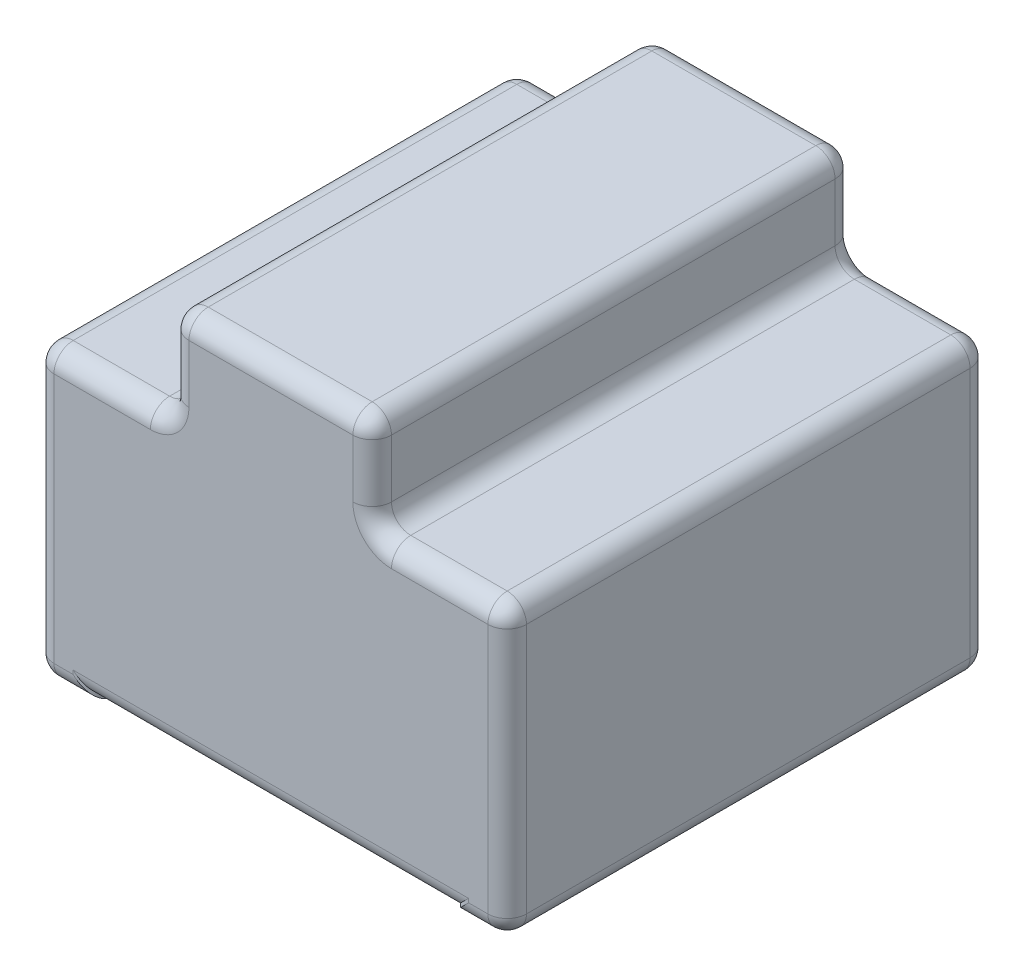
SolidWorks part; units mm, degrees
ref_plane "Front Plane" through (0, 0, 0) normal (0, 0, 1) x (1, 0, 0)
ref_plane "Top Plane" through (0, 0, 0) normal (0, 1, 0) x (1, 0, 0)
ref_plane "Right Plane" through (0, 0, 0) normal (1, 0, 0) x (0, 0, -1)
sketch "Sketch2" plane through (0, 0, 0) normal (0, 0, 1) x (1, 0, 0)
  line L0 (0, 0) -> (0, 38.1)
  line L1 (0, 38.1) -> (17.78, 38.1)
  line L2 (17.78, 38.1) -> (17.78, 50.8)
  line L3 (17.78, 50.8) -> (44.45, 50.8)
  line L4 (44.45, 50.8) -> (44.45, 38.1)
  line L5 (44.45, 38.1) -> (62.23, 38.1)
  line L6 (62.23, 38.1) -> (62.23, 0)
  line L8 (54.61, 0) -> (62.23, 0)
  line L9 (54.61, 0) -> (54.61, 0.508)
  line L10 (54.61, 0.508) -> (7.62, 0.508)
  line L11 (7.62, 0.508) -> (7.62, 0)
  line L12 (7.62, 0) -> (0, 0)
  dimension "D1" = 38.1
  dimension "D2" = 12.7
  dimension "D3" = 12.7
  dimension "D4" = 17.78
  dimension "D5" = 17.78
  dimension "D6" = 7.62
  dimension "D7" = 7.62
  dimension "D8" = 46.99
  dimension "D9" = 0.508
  dimension "D10" = 38.1
extrude "Boss-Extrude1" add sketch "Sketch2" along normal blind 58.42
sketch "Sketch3" plane through (0, 0.508, 0) normal (0, -1, 0) x (1, 0, 0)
  line L0 (7.62, 58.42) -> (54.61, 58.42) construction
  line L1 (7.62, 0) -> (54.61, 0) construction
  line L2 (7.62, 58.42) -> (7.62, 0) construction
  line L3 (54.61, 58.42) -> (54.61, 0) construction
  line L12 (10.16, 3.81) -> (52.07, 3.81)
  line L13 (52.07, 3.81) -> (52.07, 54.61)
  line L14 (52.07, 54.61) -> (10.16, 54.61)
  line L15 (10.16, 54.61) -> (10.16, 3.81)
  dimension "D1" = 3.81
  dimension "D2" = 3.81
  dimension "D3" = 2.54
  dimension "D4" = 2.54
extrude "Cut-Extrude1" cut sketch "Sketch3" against normal blind 2.54
sketch "Sketch15" plane through (0, 0.508, 0) normal (0, -1, 0) x (-1, 0, 0)
  line L0 (-52.07, -29.21) -> (-10.16, -29.21) construction
  line L1 (-52.07, -3.81) -> (-52.07, -54.61) construction
  line L2 (-10.16, -54.61) -> (-10.16, -3.81) construction
  line L3 (-52.07, -29.21) -> (-52.07, -54.61)
  line L4 (-52.07, -54.61) -> (-10.16, -54.61)
  line L6 (-10.16, -54.61) -> (-10.16, -29.21)
  line L7 (-10.16, -3.81) -> (-52.07, -3.81) construction
  line L8 (-52.07, -54.61) -> (-10.16, -54.61) construction
  line L9 (-52.07, -29.21) -> (-10.16, -29.21)
  dimension "D1" = 0
revolve "Cut-Revolve2" cut sketch "Sketch15" angle 360 about L0
sketch "Sketch17" plane through (0, 0.508, 0) normal (0, -1, 0) x (1, 0, 0)
  line L0 (52.07, 3.81) -> (52.07, 54.61) construction
  line L1 (46.99, 1.27) -> (15.24, 1.27)
  line L2 (46.99, 1.27) -> (46.99, 29.21)
  line L3 (46.99, 29.21) -> (15.24, 29.21)
  line L4 (15.24, 1.27) -> (15.24, 29.21)
  line L5 (7.62, 58.42) -> (7.62, 0) construction
  line L6 (54.61, 58.42) -> (54.61, 0) construction
  line L7 (7.62, 0) -> (54.61, 0) construction
  point P12 (52.07, 29.21)
  dimension "D1" = 0
  dimension "D2" = 7.62
  dimension "D3" = 7.62
  dimension "D4" = 1.27
revolve "Cut-Revolve3" cut sketch "Sketch17" angle 230 about L3 other way angle 20
sketch "Sketch18" plane through (0, 0.508, 0) normal (0, -1, 0) x (1, 0, 0)
  line L0 (10.16, 3.81) -> (15.24, 3.81) construction
  line L1 (52.07, 29.21) -> (46.99, 29.21)
  line L2 (52.07, 29.21) -> (52.07, 47.752)
  line L3 (52.07, 47.752) -> (46.99, 47.752)
  line L4 (46.99, 29.21) -> (46.99, 47.752)
  line L5 (10.16, 47.752) -> (15.24, 47.752)
  line L6 (10.16, 47.752) -> (10.16, 29.21)
  line L7 (10.16, 29.21) -> (15.24, 29.21)
  line L8 (15.24, 47.752) -> (15.24, 29.21)
  line L33 (52.07, 3.81) -> (52.07, 54.61) construction
  line L34 (10.16, 29.21) -> (52.07, 29.21) construction
  line L35 (10.16, 54.61) -> (52.07, 54.61) construction
  line L36 (15.24, 57.15) -> (15.24, 54.61) construction
  line L38 (46.99, 54.61) -> (46.99, 57.15) construction
  line L41 (10.16, 47.752) -> (7.62, 47.752)
  line L42 (10.16, 47.752) -> (10.16, 44.196)
  line L43 (10.16, 44.196) -> (7.62, 44.196)
  line L44 (7.62, 47.752) -> (7.62, 44.196)
  line L45 (10.16, 54.61) -> (15.24, 54.61) construction
  line L46 (52.07, 47.752) -> (54.61, 47.752)
  line L47 (52.07, 47.752) -> (52.07, 44.196)
  line L48 (52.07, 44.196) -> (54.61, 44.196)
  line L49 (54.61, 47.752) -> (54.61, 44.196)
  line L51 (10.16, 54.61) -> (10.16, 3.81) construction
  point P34 (12.7, 3.81)
  dimension "D1" = 25.4
  dimension "D2" = 6.858
  dimension "D3" = 3.556
  dimension "D4" = 6.858
  dimension "D5" = 2.54
  dimension "D6" = 0
  dimension "D7" = 3.556
  dimension "D8" = 2.54
sketch "Sketch19" plane through (0, 0, 0) normal (0, 0, -1) x (-1, 0, 0)
  line L24 (-7.62, 0) -> (0, 0)
  line L25 (0, 0) -> (0, 38.1)
  line L26 (0, 38.1) -> (-17.78, 38.1)
  line L27 (-17.78, 38.1) -> (-17.78, 50.8)
  line L28 (-17.78, 50.8) -> (-44.45, 50.8)
  line L29 (-44.45, 50.8) -> (-44.45, 38.1)
  line L30 (-44.45, 38.1) -> (-62.23, 38.1)
  line L31 (-62.23, 38.1) -> (-62.23, 0)
  line L32 (-62.23, 0) -> (-54.61, 0)
  line L33 (-54.61, 0) -> (-54.61, 0.508)
  line L34 (-54.61, 0.508) -> (-7.62, 0.508)
  line L35 (-7.62, 0.508) -> (-7.62, 0)
  line L36 (-7.62, 0) -> (0, 0)
  line L37 (0, 0) -> (0, 38.1)
  line L38 (0, 38.1) -> (-17.78, 38.1)
  line L39 (-17.78, 38.1) -> (-17.78, 50.8)
  line L40 (-17.78, 50.8) -> (-44.45, 50.8)
  line L41 (-44.45, 50.8) -> (-44.45, 38.1)
  line L42 (-44.45, 38.1) -> (-62.23, 38.1)
  line L43 (-62.23, 38.1) -> (-62.23, 0)
  line L44 (-62.23, 0) -> (-54.61, 0)
  line L45 (-54.61, 0) -> (-54.61, 0.508)
  line L46 (-54.61, 0.508) -> (-7.62, 0.508)
  line L47 (-7.62, 0.508) -> (-7.62, 0)
  dimension "D1" = 0
extrude "Boss-Extrude2" add sketch "Sketch19" along normal blind 2.54
sketch "Sketch20" plane through (0, 0, 58.42) normal (0, 0, 1) x (1, 0, 0)
  line L24 (0, 0) -> (7.62, 0)
  line L25 (7.62, 0) -> (7.62, 0.508)
  line L26 (7.62, 0.508) -> (54.61, 0.508)
  line L27 (54.61, 0.508) -> (54.61, 0)
  line L28 (54.61, 0) -> (62.23, 0)
  line L29 (62.23, 0) -> (62.23, 38.1)
  line L30 (62.23, 38.1) -> (44.45, 38.1)
  line L31 (44.45, 38.1) -> (44.45, 50.8)
  line L32 (44.45, 50.8) -> (17.78, 50.8)
  line L33 (17.78, 50.8) -> (17.78, 38.1)
  line L34 (17.78, 38.1) -> (0, 38.1)
  line L35 (0, 38.1) -> (0, 0)
  line L36 (0, 0) -> (7.62, 0)
  line L37 (7.62, 0) -> (7.62, 0.508)
  line L38 (7.62, 0.508) -> (54.61, 0.508)
  line L39 (54.61, 0.508) -> (54.61, 0)
  line L40 (54.61, 0) -> (62.23, 0)
  line L41 (62.23, 0) -> (62.23, 38.1)
  line L42 (62.23, 38.1) -> (44.45, 38.1)
  line L43 (44.45, 38.1) -> (44.45, 50.8)
  line L44 (44.45, 50.8) -> (17.78, 50.8)
  line L45 (17.78, 50.8) -> (17.78, 38.1)
  line L46 (17.78, 38.1) -> (0, 38.1)
  line L47 (0, 38.1) -> (0, 0)
  dimension "D1" = 0
extrude "Boss-Extrude3" add sketch "Sketch20" along normal blind 2.54
revolve "Cut-Revolve4" cut sketch "Sketch18" angle 340 about L34 region at (49.53, 0.508, 38.481) region at (12.7, 0.508, 38.481) region at (8.89, 0.508, 45.974)
fillet "Fillet2" radius 2.54 32 edges at (62.23, 0, 29.21) (62.23, 38.1, 29.21) (44.45, 38.1, 29.21) (0, 0, 29.21) (0, 38.1, 29.21) (17.78, 38.1, 29.21) (44.45, 50.8, 29.21) (17.78, 50.8, 29.21) (53.34, 38.1, 60.96) (53.34, 38.1, -2.54) (62.23, 19.05, 60.96) (62.23, 19.05, -2.54) (44.45, 44.45, 60.96) (44.45, 44.45, -2.54) (0, 19.05, 60.96) (0, 19.05, -2.54) (8.89, 38.1, 60.96) (8.89, 38.1, -2.54) (17.78, 44.45, 60.96) (17.78, 44.45, -2.54) (31.115, 50.8, 60.96) (31.115, 50.8, -2.54) (58.42, 0, -2.54) (54.61, 0.254, -2.54) (31.115, 0.508, -2.54) (7.62, 0.254, -2.54) (3.81, 0, -2.54) (54.61, 0.254, 60.96) (3.81, 0, 60.96) (7.62, 0.254, 60.96) (31.115, 0.508, 60.96) (58.42, 0, 60.96)
